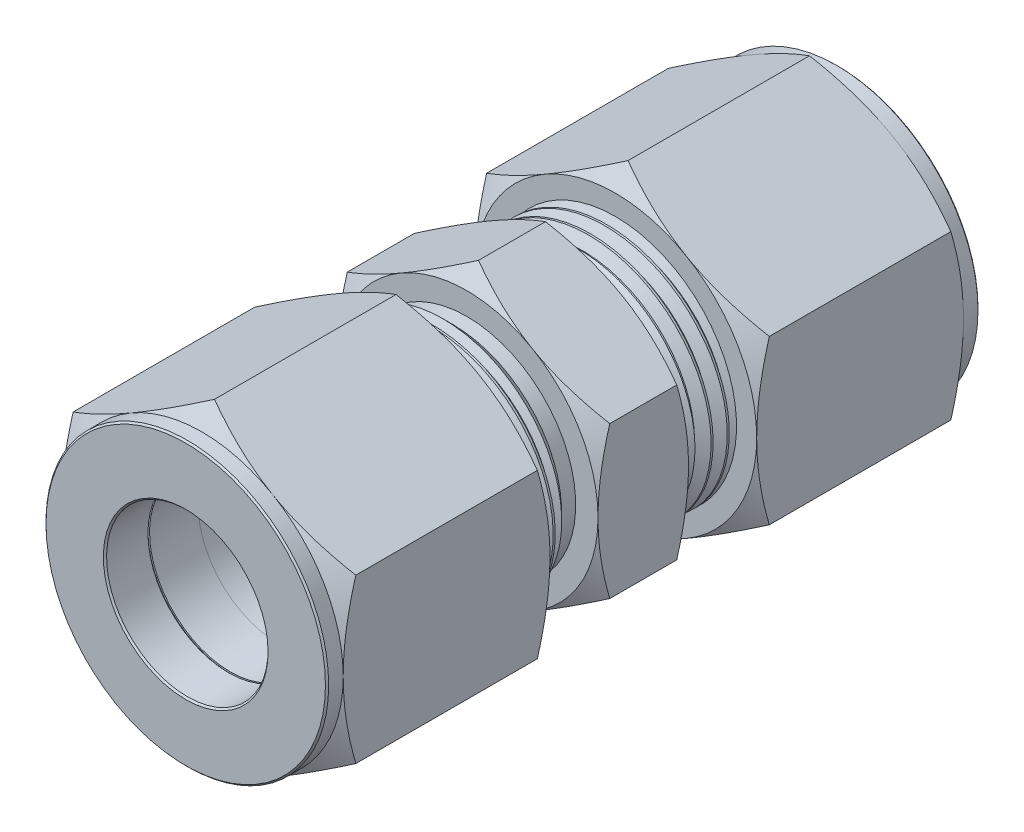
SolidWorks part; units mm, degrees
ref_plane "Front Plane" through (0, 0, 0) normal (0, 0, 1) x (1, 0, 0)
ref_plane "Top Plane" through (0, 0, 0) normal (0, 1, 0) x (1, 0, 0)
ref_plane "Right Plane" through (0, 0, 0) normal (1, 0, 0) x (0, 0, -1)
sketch "Sketch1" plane through (0, 0, 0) normal (1, 0, 0) x (0, 0, -1)
  line L0 (0, 0) -> (51.308, 0) construction
  line L1 (0, 6.35) -> (0, -6.35) construction
  line L2 (17.526, 11.1125) -> (17.526, -11.1125) construction
  line L3 (7.0104, 9.525) -> (7.0104, -9.525) construction
  line L4 (7.0104, 9.525) -> (7.0104, 8.255) construction
  line L5 (25.654, 10.3187) -> (25.654, -10.3187) construction
  line L6 (6.1976, 8.6614) -> (13.5128, 6.8834) construction
  line L7 (13.5128, 6.8834) -> (13.5128, 6.35) construction
  line L8 (13.5128, 6.35) -> (7.3152, 6.35) construction
  line L9 (7.3152, 6.35) -> (6.1976, 7.4676) construction
  line L10 (6.1976, 7.4676) -> (6.1976, 8.6614) construction
  line L11 (3.5052, 7.8359) -> (4.7752, 7.8359) construction
  line L12 (4.7752, 7.8359) -> (4.7752, 7.4676) construction
  line L13 (4.7752, 7.4676) -> (6.1976, 7.4676) construction
  line L14 (25.654, 5.1562) -> (25.654, -5.1562) construction
  line L15 (6.1976, 7.4676) -> (6.1976, 6.35) construction
  line L16 (7.3152, 6.35) -> (3.5052, 6.35) construction
  line L17 (3.5052, 6.35) -> (3.5052, 7.8359) construction
  line L18 (6.1976, 6.35) -> (7.3152, 6.35) construction
  line L19 (0, 6.35) -> (3.5052, 6.35) construction
  line L20 (3.5052, 6.35) -> (7.0104, 6.35) construction
  point P4 (1.778, 0)
  point P10 (7.0104, 0)
  point P12 (17.526, 0)
  point P15 (22.098, 0)
  point P16 (10.16, 0)
  point P17 (22.86, 0)
  point P33 (25.654, 0)
sketch "Sketch2" plane through (0, 0, 0) normal (0, 0, 1) x (1, 0, 0)
  line L0 (0, 6.35) -> (0, -6.35) construction
  line L1 (0, 12.8316) -> (-11.1125, 6.4158)
  line L2 (-11.1125, 6.4158) -> (-11.1125, -6.4158)
  line L3 (-11.1125, -6.4158) -> (0, -12.8316)
  line L4 (0, -12.8316) -> (11.1125, -6.4158)
  line L5 (11.1125, -6.4158) -> (11.1125, 6.4158)
  line L6 (11.1125, 6.4158) -> (0, 12.8316)
  line L7 (0, 12.8316) -> (0, 0) construction
  circle A0 centre (0, 0) radius 11.1125 construction
extrude "Boss-Extrude1" add sketch "Sketch2" against normal up to vertex (17.526 mm away) up to point (0, 0, -17.526)
sketch "Sketch3" plane through (0, 0, 0) normal (1, 0, 0) x (0, 0, -1)
  line L0 (0, 12.8316) -> (0, 11.1125)
  line L1 (0, 6.4158) -> (0, 12.8316) construction
  line L2 (0, 11.1125) -> (1.27, 11.1125)
  line L3 (1.27, 11.1125) -> (2.2625, 12.8316)
  line L4 (17.526, 12.8316) -> (0, 12.8316) construction
  line L5 (2.2625, 12.8316) -> (16.5335, 12.8316)
  line L6 (16.5335, 12.8316) -> (17.526, 11.1125)
  line L7 (17.526, 11.1125) -> (17.526, 12.8316)
  line L8 (17.526, 12.8316) -> (17.526, 14.5507)
  line L9 (17.526, 14.5507) -> (0, 14.5507)
  line L10 (0, 14.5507) -> (0, 12.8316)
  line L11 (0, 6.35) -> (0, 0)
  line L12 (0, 6.35) -> (0, -6.35) construction
  line L13 (0, 0) -> (17.526, 0)
  line L14 (17.526, 11.1125) -> (17.526, -11.1125) construction
  line L15 (17.526, 0) -> (17.526, 9.525)
  line L16 (17.526, 9.525) -> (7.0104, 9.525)
  line L17 (7.0104, 9.525) -> (7.0104, 8.255) construction
  line L18 (7.0104, 8.255) -> (3.5052, 8.255) construction
  line L19 (3.5052, 8.255) -> (3.5052, 6.35)
  line L20 (3.5052, 6.35) -> (0, 6.35)
  line L21 (3.5052, 8.255) -> (3.5052, 9.525) construction
  line L22 (3.5052, 9.525) -> (7.0104, 9.525) construction
  line L23 (7.0104, 8.89) -> (3.5052, 8.89)
  line L24 (3.5052, 8.89) -> (3.5052, 8.255)
  line L25 (7.0104, 8.89) -> (7.0104, 9.525)
  dimension "D1" = 30
  dimension "D2" = 1.27
revolve "Cut-Revolve1" cut sketch "Sketch3" angle 360 about L0
chamfer "Chamfer1" distance 0.127 angle 45 3 edges at (0, -6.35, 0) (0, -6.35, -3.5052) (11.1125, 0, 0)
sketch "Sketch4" plane through (0, 0, 0) normal (1, 0, 0) x (0, 0, -1)
  line L1 (25.654, 0) -> (10.16, 0)
  line L2 (25.654, 0) -> (25.654, 9.525)
  line L3 (25.654, 9.525) -> (10.16, 9.525)
  line L4 (10.16, 0) -> (10.16, 9.525)
  dimension "D1" = 15.494
revolve "Revolve1" add sketch "Sketch4" angle 360 about L1
sketch "Sketch5" plane through (0, 0, -10.16) normal (0, 0, -1) x (-1, 0, 0)
  circle A0 centre (0, 0) radius 9.525 construction
  circle A1 centre (0, 0) radius 9.525
  point P3 (0, 9.525)
curve "Helix/Spiral1" pitch 1.27 height 16.764 turns 13.2
sketch "Sketch6" plane through (0, 0, 0) normal (1, 0, 0) x (0, 0, -1)
  line L0 (8.9694, 9.6625) -> (10.2394, 9.6625) construction
  line L1 (10.2394, 9.6625) -> (9.6044, 8.5626) construction
  line L2 (9.6044, 8.5626) -> (8.9694, 9.6625) construction
  line L3 (9.525, 8.7001) -> (9.6837, 8.7001) construction
  line L4 (9.0488, 9.525) -> (10.16, 9.525) construction
  line L5 (9.6044, 8.5626) -> (9.6044, 8.7001) construction
  line L6 (9.6044, 9.525) -> (9.6044, 9.6625) construction
  line L7 (9.525, 8.7001) -> (9.0091, 9.5937)
  line L8 (9.0091, 9.5937) -> (10.1997, 9.5937)
  line L9 (10.1997, 9.5937) -> (9.6837, 8.7001)
  line L10 (9.6837, 8.7001) -> (9.525, 8.7001)
  point P10 (9.6044, 9.5937)
  dimension "D1" = 1.27
  dimension "D2" = 0.1588
sweep "Cut-Sweep1" cut profiles "Sketch6" path "Helix/Spiral1" align with end faces yes
sketch "Sketch7" plane through (0, 0, -25.654) normal (0, 0, -1) x (-1, 0, 0)
  line L0 (0, 0) -> (0, 11.9151) construction
  line L1 (0, 11.9151) -> (-10.3188, 5.9575)
  line L2 (-10.3188, 5.9575) -> (-10.3188, -5.9575)
  line L3 (-10.3188, -5.9575) -> (0, -11.9151)
  line L4 (0, -11.9151) -> (10.3188, -5.9575)
  line L5 (10.3188, -5.9575) -> (10.3188, 5.9575)
  line L6 (10.3188, 5.9575) -> (0, 11.9151)
  circle A0 centre (0, 0) radius 10.3188 construction
extrude "Boss-Extrude2" add sketch "Sketch7" against normal up to vertex (3.556 mm away) up to point (0, 0, -22.098)
sketch "Sketch8" plane through (0, 0, 0) normal (1, 0, 0) x (0, 0, -1)
  line L0 (10.16, 9.6625) -> (10.16, 8.5626)
  line L1 (10.16, 8.5626) -> (11.2599, 9.6625)
  line L2 (11.2599, 9.6625) -> (10.16, 9.6625)
  line L3 (22.098, 9.6625) -> (19.8983, 9.6625)
  line L4 (19.8983, 9.6625) -> (20.9981, 8.5626)
  line L5 (20.9981, 8.5626) -> (22.098, 8.5626)
  line L6 (22.098, 8.5626) -> (22.098, 9.6625)
  line L7 (22.098, 10.3187) -> (23.0196, 11.9151)
  line L8 (22.098, 11.9151) -> (22.098, 5.9575) construction
  line L9 (22.098, 11.9151) -> (25.654, 11.9151) construction
  line L10 (23.0196, 11.9151) -> (25.654, 11.9151)
  line L11 (22.86, 5.1562) -> (25.654, 5.1562)
  line L13 (25.654, -5.9575) -> (25.654, 5.9575) construction
  line L14 (25.654, 11.9151) -> (25.654, 13.5114)
  line L15 (25.654, 13.5114) -> (22.098, 13.5114)
  line L16 (22.098, 13.5114) -> (22.098, 11.9151)
  line L17 (22.098, 11.9151) -> (22.098, 10.3187)
  line L18 (9.6044, 8.5626) -> (10.16, 8.5626) construction
  line L19 (10.2394, 9.6625) -> (10.16, 9.6625) construction
  line L20 (11.2599, 9.6625) -> (19.8983, 9.6625) construction
  line L21 (20.9981, 8.5626) -> (10.16, 8.5626) construction
  line L22 (10.16, 7.6983) -> (15.7074, 6.35)
  line L24 (10.16, 6.7352) -> (10.16, -8.7065) construction
  line L25 (6.1976, 8.6614) -> (13.5128, 6.8834) construction
  line L26 (25.654, 0) -> (10.16, 0)
  line L27 (10.16, 0) -> (10.16, 7.6983)
  line L28 (15.7074, 6.35) -> (22.86, 6.35)
  line L29 (22.86, 6.35) -> (22.86, 5.1562)
  line L30 (25.654, 5.1562) -> (25.654, 0)
  line L31 (22.86, 0) -> (22.86, 5.1562) construction
  line L32 (25.654, 10.3187) -> (25.654, -10.3187) construction
  dimension "D1" = 30
revolve "Cut-Revolve2" cut sketch "Sketch8" angle 360 about L0
sketch "Sketch9" plane through (0, 0, 0) normal (1, 0, 0) x (0, 0, -1)
  line L0 (6.1976, 8.6614) -> (6.1976, 7.4676)
  line L1 (6.1976, 7.4676) -> (7.3152, 6.35)
  line L2 (7.3152, 6.35) -> (13.5128, 6.35)
  line L3 (13.5128, 6.35) -> (13.5128, 6.8834)
  line L4 (13.5128, 6.8834) -> (6.1976, 8.6614)
revolve "Revolve2" add sketch "Sketch9" angle 360 about L0
sketch "Sketch10" plane through (0, 0, 0) normal (1, 0, 0) x (0, 0, -1)
  line L0 (3.5052, 7.8359) -> (4.7752, 7.8359)
  line L1 (4.7752, 7.8359) -> (4.7752, 7.4676)
  line L2 (4.7752, 7.4676) -> (6.1976, 7.4676)
  line L4 (6.1976, 7.4676) -> (7.3152, 6.35)
  line L5 (7.3152, 6.35) -> (3.5052, 6.35)
  line L6 (3.5052, 6.35) -> (3.5052, 7.8359)
revolve "Revolve3" add sketch "Sketch10" angle 360 about L0
ref_axis "Axis1" through (0, 0, -25.654) along (1, 0, 0)
pattern_circular "CirPattern1" count 2 over 360 about axis through (0, 0, -25.654) along (1, 0, 0) reverse direction yes of bodies 113 106 115 114
combine bodies "Combine1" operation type add bodies to combine 119 113
equation "\"D4@Helix/Spiral1\" = \"Straight Thread Pitch@Sketch1\""
equation "\"D3@Helix/Spiral1\" = \"D4@Helix/Spiral1\" + \"D1@Sketch4\""
equation "\"D1@Sketch6\" = \"D4@Helix/Spiral1\""
equation "\"D2@Sketch6\" = \"D1@Sketch6\" / 8"
